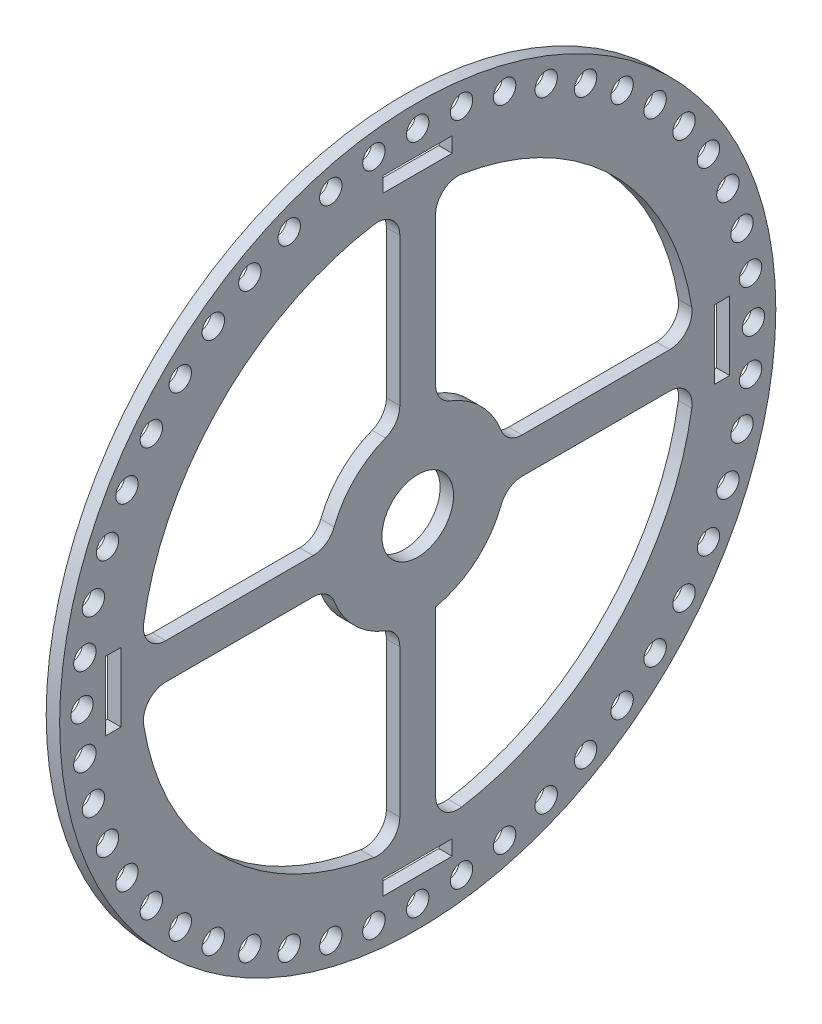
SolidWorks part; units mm, degrees
material "AISI 304"
ref_plane "Front Plane" through (0, 0, 0) normal (0, 0, 1) x (1, 0, 0)
ref_plane "Top Plane" through (0, 0, 0) normal (0, 1, 0) x (1, 0, 0)
ref_plane "Right Plane" through (0, 0, 0) normal (1, 0, 0) x (0, 0, -1)
sketch "Sketch3" plane through (0, 0, 0) normal (1, 0, 0) x (0, 0, -1)
  line L0 (9.798, 2) -> (30.9354, 2)
  line L9 (-30.9354, 2) -> (-9.798, 2)
  line L11 (-30.9354, -2) -> (-9.798, -2)
  line L13 (9.798, -2) -> (30.9354, -2)
  line L14 (-2, -9.798) -> (-2, -30.9354)
  line L16 (-2, 30.9354) -> (-2, 9.798)
  line L18 (2, 30.9354) -> (2, 9.798)
  line L19 (2, -9.798) -> (2, -30.9354)
  line L20 (0, 0) -> (0, 40) construction
  line L22 (3.85, 34.85) -> (-3.85, 34.85)
  line L23 (3.85, 34.85) -> (3.85, 33.15)
  line L24 (3.85, 33.15) -> (-3.85, 33.15)
  line L25 (-3.85, 34.85) -> (-3.85, 33.15)
  line L26 (3.85, 34.85) -> (-3.85, 33.15) construction
  line L27 (3.85, 33.15) -> (-3.85, 34.85) construction
  line L39 (33.15, -3.85) -> (33.15, 3.85)
  line L40 (34.85, 3.85) -> (33.15, 3.85)
  line L41 (34.85, -3.85) -> (34.85, 3.85)
  line L42 (34.85, -3.85) -> (33.15, -3.85)
  line L43 (-3.85, -33.15) -> (3.85, -33.15)
  line L44 (3.85, -34.85) -> (3.85, -33.15)
  line L45 (-3.85, -34.85) -> (3.85, -34.85)
  line L46 (-3.85, -34.85) -> (-3.85, -33.15)
  line L47 (-33.15, 3.85) -> (-33.15, -3.85)
  line L48 (-34.85, -3.85) -> (-33.15, -3.85)
  line L49 (-34.85, 3.85) -> (-34.85, -3.85)
  line L50 (-34.85, 3.85) -> (-33.15, 3.85)
  circle A0 centre (0, 0) radius 40
  arc A1 (30.9354, 2) -> (2, 30.9354) centre (0, 0) ccw
  arc A2 (9.798, 2) -> (2, 9.798) centre (0, 0) ccw
  arc A3 (-9.798, -2) -> (-2, -9.798) centre (0, 0) ccw
  arc A4 (-30.9354, -2) -> (-2, -30.9354) centre (0, 0) ccw
  arc A5 (2, -30.9354) -> (30.9354, -2) centre (0, 0) ccw
  arc A6 (2, -9.798) -> (9.798, -2) centre (0, 0) ccw
  arc A7 (-2, 9.798) -> (-9.798, 2) centre (0, 0) ccw
  arc A8 (-2, 30.9354) -> (-30.9354, 2) centre (0, 0) ccw
  circle A9 centre (0, 0) radius 4
  point P20 (0, 34)
  point P41 (1.15, 0)
  point P42 (0, 0)
  dimension "D1" = 80
  dimension "D2" = 62
  dimension "D5" = 20
  dimension "D8" = 8
  dimension "D3" = 4
  dimension "D4" = 2
  dimension "D6" = 2
  dimension "D7" = 4
  dimension "D9" = 6
  dimension "D10" = 7.7
  dimension "D11" = 1.7
  dimension "D12" = 4
extrude "Boss-Extrude2" add sketch "Sketch3" along normal blind 1.5
sketch "Sketch4" plane through (0, 0, 0) normal (-1, 0, 0) x (0, 0, 1)
  line L0 (0, 0) -> (0, 37.5) construction
  circle A0 centre (0, 37.5) radius 1.25
  point P2 (0, 21.5438)
  dimension "D1" = 2.5
  dimension "D2" = 37.5
extrude "Cut-Extrude1" cut sketch "Sketch4" against normal blind 1.5 contours A0
pattern_circular "CirPattern1" count 48 over 360 about axis through (0, 0, 0) along (1, 0, 0) of "Cut-Extrude1"
fillet "Fillet1" radius 2.5 15 edges at (0.75, -2, 30.9354) (0.75, -30.9354, 2) (0.75, -9.798, 2) (0.75, -2, 9.798) (0.75, -30.9354, -2) (0.75, -2, -30.9354) (0.75, 2, -9.798) (0.75, 2, -30.9354) (0.75, 2, 9.798) (0.75, 2, 30.9354) (0.75, 9.798, 2) (0.75, 30.9354, 2) (0.75, 9.798, -2) (0.75, 30.9354, -2) (0.75, -2, -9.798)
